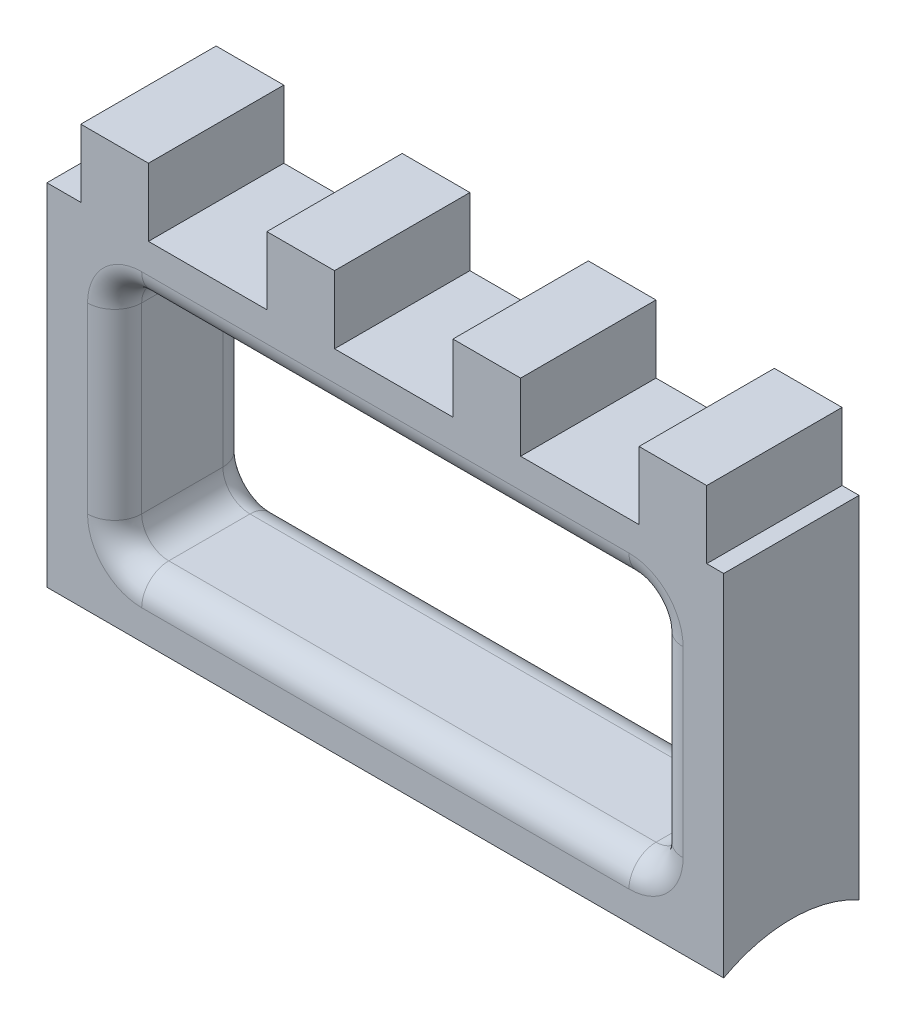
SolidWorks part; units mm, degrees
ref_plane "Front Plane" through (0, 0, 0) normal (0, 0, 1) x (1, 0, 0)
ref_plane "Top Plane" through (0, 0, 0) normal (0, 1, 0) x (1, 0, 0)
ref_plane "Right Plane" through (0, 0, 0) normal (1, 0, 0) x (0, 0, -1)
sketch "Sketch1" plane through (0, 0, 0) normal (0, 1, 0) x (1, 0, 0)
  line L0 (31.75, 0) -> (-31.75, 0) construction
  line L1 (31.75, -6.35) -> (-31.75, -6.35)
  line L2 (31.75, -6.35) -> (31.75, 6.35)
  line L3 (31.75, 6.35) -> (-31.75, 6.35)
  line L4 (-31.75, -6.35) -> (-31.75, 6.35)
  line L5 (31.75, -6.35) -> (-31.75, 6.35) construction
  line L6 (31.75, 6.35) -> (-31.75, -6.35) construction
  line L7 (-4.765, -6.35) -> (-4.765, 6.35)
  line L8 (-22.225, -6.35) -> (-28.575, -6.35)
  line L9 (-22.225, -6.35) -> (-22.225, 6.35)
  line L10 (-22.225, 6.35) -> (-28.575, 6.35)
  line L11 (-28.575, -6.35) -> (-28.575, 6.35)
  line L12 (-22.225, -6.35) -> (-28.575, 6.35) construction
  line L13 (-22.225, 6.35) -> (-28.575, -6.35) construction
  line L14 (-11.115, -6.35) -> (-11.115, 6.35)
  line L15 (12.695, -6.35) -> (12.695, 6.35)
  line L16 (6.345, -6.35) -> (6.345, 6.35)
  line L17 (30.155, -6.35) -> (30.155, 6.35)
  line L18 (23.805, -6.35) -> (23.805, 6.35)
  line L19 (-22.225, -6.35) -> (-4.765, -6.35) construction
  point P0 (0, 0)
  point P8 (-25.4, 0)
  dimension "D1" = 12.7
  dimension "D2" = 63.5
  dimension "D3" = 12.7
  dimension "D4" = 6.35
  dimension "D5" = 3.175
  dimension "D7" = 17.46
  dimension "D6" = 4
extrude "Boss-Extrude1" add sketch "Sketch1" along normal blind 6.35 contours L1 L11 L3 L4 | L1 L14 L3 L9 | L1 L16 L3 L7 | L1 L18 L3 L15 | L17 L1 L2 L3 region at (30.9525, 0, 0) region at (18.25, 0, 0) region at (0.79, 0, 0) region at (-16.67, 0, 0) region at (-30.1625, 0, 0)
extrude "Boss-Extrude2" add sketch "Sketch1<3>" along normal blind 12.7 contours L11 L1 L9 L3 | L14 L1 L7 L3 | L16 L1 L15 L3 | L18 L1 L17 L3 region at (26.98, 0, 0) region at (9.52, 0, 0) region at (-7.94, 0, 0) region at (-25.4, 0, 0)
sketch "Sketch1<3>" plane through (0, 0, 0) normal (0, 1, 0) x (1, 0, 0) same geometry as "Sketch1"
sketch "Sketch3" plane through (0, 0, 0) normal (0, -1, 0) x (-1, 0, 0)
  line L1 (-31.75, 6.35) -> (31.75, 6.35)
  line L2 (-31.75, 6.35) -> (-31.75, -6.35)
  line L3 (-31.75, -6.35) -> (31.75, -6.35)
  line L4 (31.75, 6.35) -> (31.75, -6.35)
extrude "Boss-Extrude3" add sketch "Sketch3" along normal blind 38.1
sketch "Sketch4" plane through (31.75, 0, 0) normal (1, 0, 0) x (0, 0, -1)
  line L0 (6.35, -38.1) -> (-6.35, -38.1) construction
  line L1 (-6.35, 6.35) -> (-6.35, -38.1) construction
  line L2 (6.35, 6.35) -> (6.35, -38.1) construction
  line L3 (6.35, -26.5186) -> (6.35, -38.1)
  line L4 (6.35, -38.1) -> (-6.35, -38.1)
  line L5 (-6.35, -38.1) -> (-6.35, -26.5186)
  arc A0 (-6.35, -26.5186) -> (6.35, -26.5186) centre (0, -38.1) cw
extrude "Cut-Extrude1" cut sketch "Sketch4" against normal through all
sketch "Sketch5" plane through (0, 0, 6.35) normal (0, 0, 1) x (1, 0, 0)
  line L0 (-31.75, -10.0843) -> (31.75, -10.0843) construction
  line L1 (-31.75, 6.35) -> (-31.75, -26.5186) construction
  line L2 (31.75, 6.35) -> (31.75, -26.5186) construction
  line L4 (25.4, -21.1968) -> (-25.4, -21.1968)
  line L5 (25.4, -21.1968) -> (25.4, 1.0282)
  line L6 (25.4, 1.0282) -> (-25.4, 1.0282)
  line L7 (-25.4, -21.1968) -> (-25.4, 1.0282)
  line L8 (25.4, -21.1968) -> (-25.4, 1.0282) construction
  line L9 (25.4, 1.0282) -> (-25.4, -21.1968) construction
  point P6 (0, -10.0843)
  dimension "D1" = 50.8
  dimension "D2" = 22.225
extrude "Cut-Extrude2" cut sketch "Sketch5" against normal through all
fillet "Fillet1" radius 2.54 12 edges at (25.4, -10.0843, 6.35) (25.4, -10.0843, -6.35) (0, -21.1968, 6.35) (0, -21.1968, -6.35) (-25.4, -10.0843, -6.35) (-25.4, -10.0843, 6.35) (0, 1.0282, -6.35) (0, 1.0282, 6.35) (-25.4, 1.0282, 0) (-25.4, -21.1968, 0) (25.4, -21.1968, 0) (25.4, 1.0282, 0)
